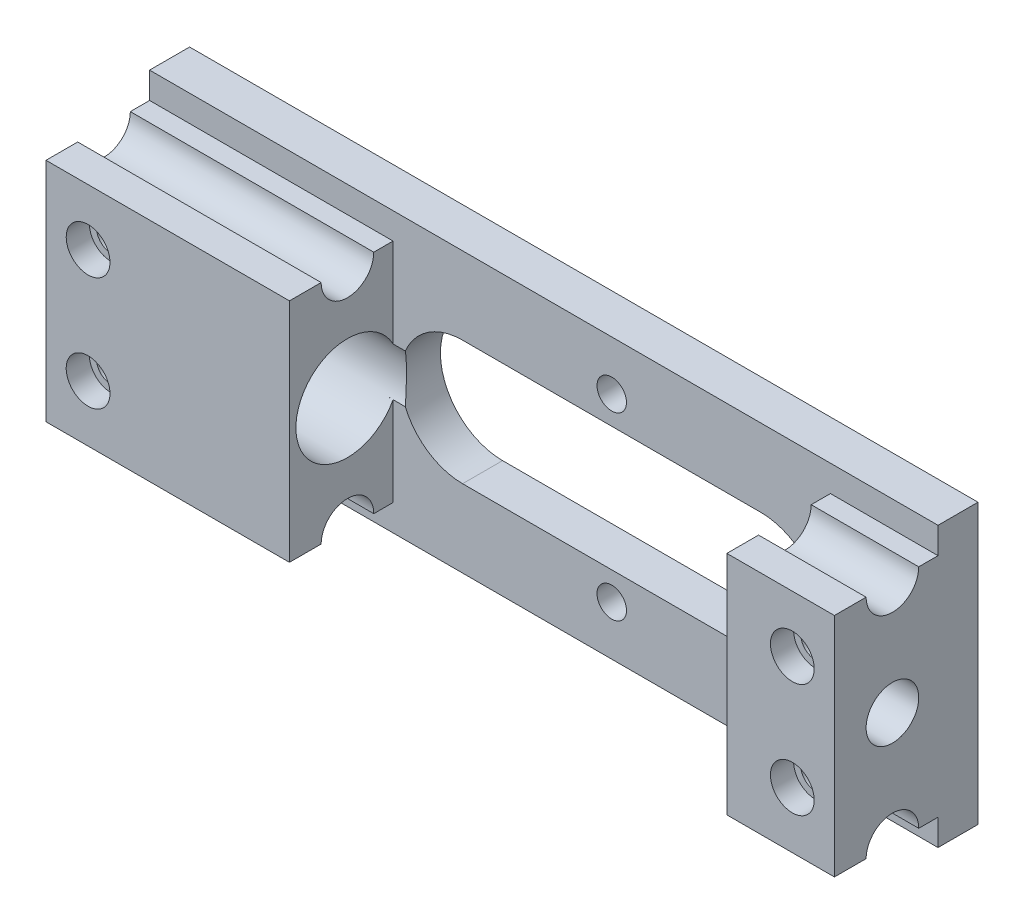
SolidWorks part; units mm, degrees
ref_plane "Front Plane" through (0, 0, 0) normal (0, 0, 1) x (1, 0, 0)
ref_plane "Top Plane" through (0, 0, 0) normal (0, 1, 0) x (1, 0, 0)
ref_plane "Right Plane" through (0, 0, 0) normal (1, 0, 0) x (0, 0, -1)
sketch "Sketch1" plane through (0, 0, 0) normal (0, 0, 1) x (1, 0, 0)
  line L1 (-22.0345, -8.4201) -> (22.0345, -8.4201)
  line L2 (-22.0345, -8.4201) -> (-22.0345, 8.4201)
  line L3 (-22.0345, 8.4201) -> (22.0345, 8.4201)
  line L4 (22.0345, -8.4201) -> (22.0345, 8.4201)
  line L5 (-22.0345, -8.4201) -> (22.0345, 8.4201) construction
  line L6 (-22.0345, 8.4201) -> (22.0345, -8.4201) construction
  point P0 (0, 0)
  dimension "D1" = 44.069
  dimension "D2" = 16.8402
extrude "Boss-Extrude1" add sketch "Sketch1" along normal blind 7.1628
sketch "Sketch2" plane through (0, 0, 7.1628) normal (0, 0, 1) x (1, 0, 0)
  line L0 (-22.0345, 0) -> (22.0345, 0) construction
  line L1 (-10.8458, 8.4201) -> (15.5448, 8.4201)
  line L2 (-10.8458, 8.4201) -> (-10.8458, -8.4201)
  line L3 (-10.8458, -8.4201) -> (15.5448, -8.4201)
  line L4 (15.5448, 8.4201) -> (15.5448, -8.4201)
  line L5 (-22.0345, 8.4201) -> (-22.0345, -8.4201) construction
  line L6 (22.0345, -8.4201) -> (22.0345, 8.4201) construction
  line L7 (-10.8458, 8.4201) -> (-22.0345, 0) construction
  line L8 (-22.0345, 0) -> (-10.8458, -8.4201) construction
  line L9 (2.3495, 8.4201) -> (2.3495, -8.4201) construction
  line L12 (22.0345, 8.4201) -> (-22.0345, 8.4201) construction
  dimension "D1" = 26.3906
  dimension "D2" = 24.384
extrude "Cut-Extrude1" cut sketch "Sketch2" against normal blind 4.75
sketch "Sketch4" plane through (0, 0, 7.1628) normal (0, 0, 1) x (1, 0, 0)
  line L0 (-10.8458, 8.4201) -> (-10.8458, -8.4201) construction
  line L1 (-22.0345, -8.4201) -> (-10.8458, -8.4201)
  line L2 (-22.0345, -8.4201) -> (-22.0345, -6.8326)
  line L3 (-22.0345, -6.8326) -> (-10.8458, -6.8326)
  line L4 (-10.8458, -8.4201) -> (-10.8458, -6.8326)
  line L5 (-22.0345, 0) -> (-10.8458, 0) construction
  line L6 (-22.0345, 8.4201) -> (-22.0345, -8.4201) construction
  line L7 (-10.8458, 8.4201) -> (-10.8458, -8.4201) construction
  line L8 (-10.8458, 8.4201) -> (-10.8458, 6.8326)
  line L9 (-22.0345, 6.8326) -> (-10.8458, 6.8326)
  line L10 (-22.0345, 8.4201) -> (-22.0345, 6.8326)
  line L11 (-22.0345, 8.4201) -> (-10.8458, 8.4201)
  line L12 (22.0345, -8.4201) -> (22.0345, 8.4201) construction
  line L13 (15.5448, -8.4201) -> (22.0345, -8.4201)
  line L14 (15.5448, -8.4201) -> (15.5448, -6.8326)
  line L15 (15.5448, -6.8326) -> (22.0345, -6.8326)
  line L16 (22.0345, -8.4201) -> (22.0345, -6.8326)
  line L17 (15.5448, 6.8326) -> (22.0345, 6.8326)
  line L18 (22.0345, 8.4201) -> (22.0345, 6.8326)
  line L19 (15.5448, 8.4201) -> (22.0345, 8.4201)
  line L20 (15.5448, 8.4201) -> (15.5448, 6.8326)
  dimension "D1" = 1.5875
extrude "Cut-Extrude9" cut sketch "Sketch4" against normal up to surface (4.75 mm away) up to face at (2.3495, 0, 2.4128)
sketch "Sketch5" plane through (-22.0345, 0, 0) normal (-1, 0, 0) x (0, 0, 1)
  line L1 (0, 0) -> (7.1628, 0) construction
  line L2 (0, 8.4201) -> (0, -8.4201) construction
  line L3 (7.1628, 6.8326) -> (7.1628, -6.8326) construction
  circle A0 centre (5.1628, -6.8326) radius 1.5875
  circle A1 centre (5.1628, 6.8326) radius 1.5875
  dimension "D1" = 3.175
  dimension "D2" = 2
extrude "Cut-Extrude10" cut sketch "Sketch5" against normal through all
sketch "Sketch14" plane through (0, 0, 7.1628) normal (0, 0, 1) x (1, 0, 0)
  line L4 (-10.8458, -6.8326) -> (-10.8458, 6.8326)
  line L5 (-10.8458, 6.8326) -> (-22.0345, 6.8326)
  line L6 (-22.0345, 6.8326) -> (-22.0345, -6.8326)
  line L7 (-22.0345, -6.8326) -> (-10.8458, -6.8326)
  line L8 (-10.8458, -6.8326) -> (-10.8458, 6.8326)
  line L9 (-10.8458, 6.8326) -> (-22.0345, 6.8326)
  line L10 (-22.0345, 6.8326) -> (-22.0345, -6.8326)
  line L11 (-22.0345, -6.8326) -> (-10.8458, -6.8326)
  line L12 (22.0345, -6.8326) -> (22.0345, 6.8326)
  line L13 (22.0345, 6.8326) -> (15.5448, 6.8326)
  line L14 (15.5448, 6.8326) -> (15.5448, -6.8326)
  line L15 (15.5448, -6.8326) -> (22.0345, -6.8326)
  line L16 (22.0345, -6.8326) -> (22.0345, 6.8326)
  line L17 (22.0345, 6.8326) -> (15.5448, 6.8326)
  line L18 (15.5448, 6.8326) -> (15.5448, -6.8326)
  line L19 (15.5448, -6.8326) -> (22.0345, -6.8326)
  dimension "D1" = 0
  dimension "D2" = 0
extrude "Boss-Extrude3" add sketch "Sketch14" along normal blind 1.5
sketch "Sketch6" plane through (0, 0, 8.6628) normal (0, 0, 1) x (1, 0, 0)
  line L0 (-22.0345, 0) -> (-10.8458, 0) construction
  line L2 (-10.8458, 6.8326) -> (-10.8458, -6.8326) construction
  line L3 (-22.0345, 6.8326) -> (-22.0345, -6.8326) construction
  circle A0 centre (-14.7955, 3.429) radius 0.889
  circle A1 centre (-14.7955, -3.429) radius 0.889
  circle A2 centre (19.4945, 3.429) radius 0.889
  circle A3 centre (19.4945, -3.429) radius 0.889
  dimension "D1" = 1.778
  dimension "D2" = 6.858
  dimension "D3" = 7.239
  dimension "D4" = 2
extrude "Cut-Extrude11" cut sketch "Sketch6" against normal through all contours A2 | A3 region at (19.4945, 3.429, 8.6628) region at (19.4945, -3.429, 8.6628)
sketch "Sketch7" plane through (0, 0, 8.6628) normal (0, 0, 1) x (1, 0, 0)
  circle A2 centre (19.4945, 3.429) radius 1.3208
  circle A3 centre (19.4945, -3.429) radius 1.3208
extrude "Cut-Extrude12" cut sketch "Sketch7" against normal blind 1.397
sketch "Sketch9" plane through (0, 0, 0) normal (0, 0, -1) x (-1, 0, 0)
  line L0 (22.0345, 8.4201) -> (22.0345, -8.4201) construction
  line L1 (-22.0345, 0) -> (22.0345, 0) construction
  line L2 (-22.0345, -8.4201) -> (-22.0345, 8.4201) construction
  circle A0 centre (-2.3495, 5.4356) radius 0.889
  circle A1 centre (-2.3495, -5.4356) radius 0.889
  dimension "D1" = 1.778
  dimension "D2" = 24.384
  dimension "D3" = 10.8712
extrude "Cut-Extrude13" cut sketch "Sketch9" against normal through all
sketch "Sketch10" plane through (0, 0, 0) normal (0, 0, -1) x (-1, 0, 0)
  line L0 (-22.0345, 0) -> (22.0345, 0) construction
  line L1 (-22.0345, -8.4201) -> (-22.0345, 8.4201) construction
  line L2 (22.0345, 8.4201) -> (22.0345, -8.4201) construction
  circle A0 centre (-2.3495, 5.4356) radius 1.1906
  circle A1 centre (-2.3495, -5.4356) radius 1.1906
  dimension "D1" = 2.3813
extrude "Cut-Extrude14" cut sketch "Sketch10" against normal blind 1
sketch "Sketch11" plane through (0, 0, 0) normal (0, 0, -1) x (-1, 0, 0)
  line L0 (-22.0345, 0) -> (22.0345, 0) construction
  line L1 (-22.0345, -8.4201) -> (-22.0345, 8.4201) construction
  line L2 (22.0345, 8.4201) -> (22.0345, -8.4201) construction
  line L3 (-2.3495, 5.4356) -> (-2.3495, -5.4356) construction
  line L4 (-11.3495, 0) -> (6.6505, 0) construction
  line L5 (-11.3495, 3.75) -> (6.6505, 3.75)
  line L6 (-11.3495, -3.75) -> (6.6505, -3.75)
  arc A0 (-11.3495, 3.75) -> (-11.3495, -3.75) centre (-11.3495, 0) ccw
  arc A1 (6.6505, -3.75) -> (6.6505, 3.75) centre (6.6505, 0) ccw
  point P12 (-2.3495, 0)
  dimension "D1" = 7.5
  dimension "D2" = 18
extrude "Cut-Extrude15" cut sketch "Sketch11" against normal through all
sketch "Sketch12" plane through (-10.8458, 0, 0) normal (1, 0, 0) x (0, 0, -1)
  circle A0 centre (-5.1628, 0) radius 3.1115
  dimension "D1" = 6.223
extrude "Cut-Extrude16" cut sketch "Sketch12" against normal blind 10.922 and the other way up to next
sketch "Sketch15" plane through (-22.0345, 0, 0) normal (-1, 0, 0) x (0, 0, 1)
  line L10 (8.6628, 6.8326) -> (6.7503, 6.8326)
  line L11 (3.5753, 6.8326) -> (2.4128, 6.8326)
  line L12 (2.4128, 6.8326) -> (2.4128, 8.4201)
  line L13 (2.4128, 8.4201) -> (0, 8.4201)
  line L14 (0, 8.4201) -> (0, -8.4201)
  line L15 (0, -8.4201) -> (2.4128, -8.4201)
  line L16 (2.4128, -8.4201) -> (2.4128, -6.8326)
  line L17 (2.4128, -6.8326) -> (3.5753, -6.8326)
  line L18 (6.7503, -6.8326) -> (8.6628, -6.8326)
  line L19 (8.6628, -6.8326) -> (8.6628, 6.8326)
  line L20 (8.6628, 6.8326) -> (6.7503, 6.8326)
  line L21 (3.5753, 6.8326) -> (2.4128, 6.8326)
  line L22 (2.4128, 6.8326) -> (2.4128, 8.4201)
  line L23 (2.4128, 8.4201) -> (0, 8.4201)
  line L24 (0, 8.4201) -> (0, -8.4201)
  line L25 (0, -8.4201) -> (2.4128, -8.4201)
  line L26 (2.4128, -8.4201) -> (2.4128, -6.8326)
  line L27 (2.4128, -6.8326) -> (3.5753, -6.8326)
  line L28 (6.7503, -6.8326) -> (8.6628, -6.8326)
  line L29 (8.6628, -6.8326) -> (8.6628, 6.8326)
  arc A2 (3.5753, 6.8326) -> (6.7503, 6.8326) centre (5.1628, 6.8326) ccw
  arc A3 (6.7503, -6.8326) -> (3.5753, -6.8326) centre (5.1628, -6.8326) ccw
  arc A4 (3.5753, 6.8326) -> (6.7503, 6.8326) centre (5.1628, 6.8326) ccw
  arc A5 (6.7503, -6.8326) -> (3.5753, -6.8326) centre (5.1628, -6.8326) ccw
  dimension "D1" = 0
extrude "Boss-Extrude4" add sketch "Sketch15" along normal blind 3.5
ref_plane "Plane1" through (-1.75, 0, 0) normal (1, 0, 0) x (0, 0, -1)
mirror "Mirror1" about plane through (-1.75, 0, 0) normal (1, 0, 0) of "Cut-Extrude11", "Cut-Extrude12"
sketch "Sketch16" plane through (22.0345, 0, 0) normal (1, 0, 0) x (0, 0, -1)
  circle A0 centre (-5.1628, 0) radius 1.5875
  dimension "D1" = 3.175
extrude "Cut-Extrude17" cut sketch "Sketch16" against normal up to next
